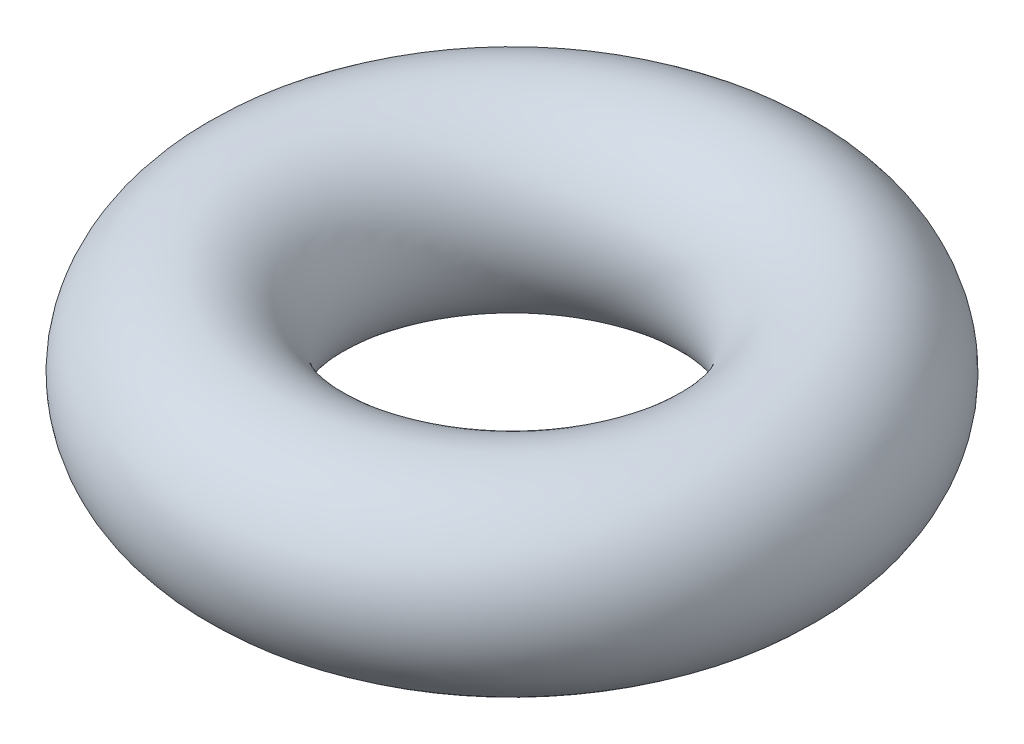
SolidWorks part; units mm, degrees
ref_plane "Front Plane" through (0, 0, 0) normal (0, 0, 1) x (1, 0, 0)
ref_plane "Top Plane" through (0, 0, 0) normal (0, 1, 0) x (1, 0, 0)
ref_plane "Right Plane" through (0, 0, 0) normal (1, 0, 0) x (0, 0, -1)
sketch "Sketch1" plane through (0, 0, 0) normal (0, 0, 1) x (1, 0, 0)
  line L0 (0, 25.4) -> (0, -25.4) construction
  circle A0 centre (63.5, 0) radius 25.4
  dimension "D1" = 50.8
  dimension "D2" = 50.8
  dimension "D3" = 25.4
  dimension "D4" = 63.5
revolve "Revolve1" add sketch "Sketch1" angle 360 about L0
ref_axis "Axis1" through (0, -27.94, 0) along (0, 1, 0)
